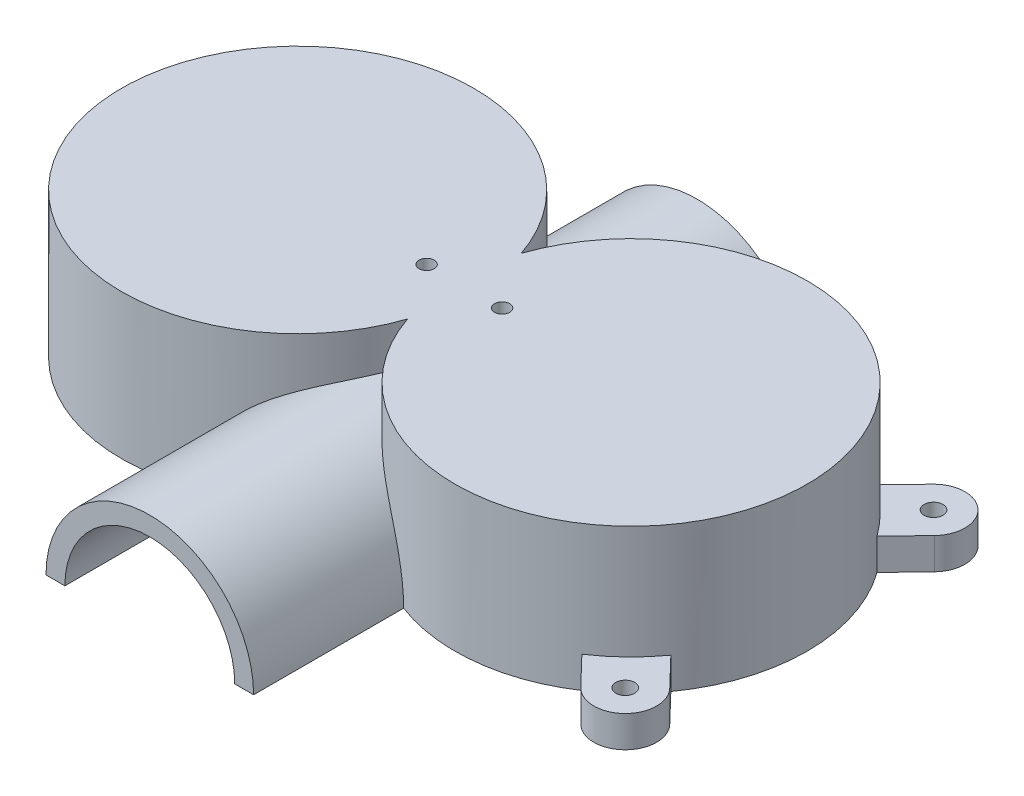
SolidWorks part; units mm, degrees
ref_plane "Front Plane" through (0, 0, 0) normal (0, 0, 1) x (1, 0, 0)
ref_plane "Top Plane" through (0, 0, 0) normal (0, 1, 0) x (1, 0, 0)
ref_plane "Right Plane" through (0, 0, 0) normal (1, 0, 0) x (0, 0, -1)
sketch "Sketch1" plane through (0, 0, 0) normal (0, 1, 0) x (1, 0, 0)
  line L0 (-26.5, 0) -> (26.5, 0) construction
  arc A0 (0, 9.0416) -> (0, -9.0416) centre (-26.5, 0) ccw
  arc A1 (0, -9.0416) -> (0, 9.0416) centre (26.5, 0) ccw
  dimension "D2" = 56
  dimension "D1" = 53
extrude "Boss-Extrude1" add sketch "Sketch1" along normal blind 23 contours A0 A1
shell "Shell1" [suppressed] thickness 3
sketch "Sketch2" plane through (0, 0, 0) normal (0, 1, 0) x (1, 0, 0)
  line L0 (-33.5, 33) -> (-33.5, 27.1109)
  line L1 (-23.5, 33) -> (-23.5, 27.8388)
  circle A0 centre (-28.5, 33) radius 1.5
  arc A1 (-23.5, 33) -> (-33.5, 33) centre (-28.5, 33) ccw
  arc A2 (-23.5, 27.8388) -> (-33.5, 27.1109) centre (-26.5, 0) ccw
  dimension "D3" = 3
  dimension "D4" = 10
  dimension "D5" = 56
  dimension "D1" = 33
  dimension "D2" = 28.5
  dimension "D6" = 26.5
extrude "Boss-Extrude2" add sketch "Sketch2" along normal blind 5
sketch "Sketch3" plane through (0, 0, 0) normal (0, 1, 0) x (1, 0, 0)
  line L0 (50.0744, 24.5) -> (50.0744, -24.5) construction
  line L1 (26.5, 0) -> (50.0744, -24.5) construction
  line L2 (0, 0) -> (50.0744, 0) construction
  line L3 (50.0744, 24.5) -> (26.5, 0) construction
  line L4 (46.4714, -27.9668) -> (41.9992, -23.319)
  line L5 (53.6773, -21.0332) -> (49.2051, -16.3854)
  line L6 (46.4714, 27.9668) -> (41.9992, 23.319)
  line L7 (53.6773, 21.0332) -> (49.2051, 16.3854)
  circle A0 centre (50.0744, 24.5) radius 1.5
  circle A1 centre (50.0744, -24.5) radius 1.5
  arc A2 (50.0744, 15.1079) -> (41.9992, 23.319) centre (26.5, 0) ccw
  arc A3 (53.6773, 21.0332) -> (46.4714, 27.9668) centre (50.0744, 24.5) ccw
  arc A4 (46.4714, -27.9668) -> (53.6773, -21.0332) centre (50.0744, -24.5) ccw
  arc A6 (41.9992, -23.319) -> (50.0744, -15.1079) centre (26.5, 0) ccw
  dimension "D3" = 56
  dimension "D5" = 3
  dimension "D6" = 10
  dimension "D1" = 49
  dimension "D2" = 26.5
  dimension "D4" = 34
extrude "Boss-Extrude3" add sketch "Sketch3" along normal blind 5 contours L7 A3 L6 A2 A0 | A6 L4 A4 L5 A1 region at (44.3687, 0, 25.5145) region at (53.4128, 0, -27.9695)
sketch "Sketch6" plane through (0, 0, 0) normal (0, 0, 1) x (1, 0, 0)
  line L0 (-16.5, 0) -> (16.5, 0)
  arc A0 (16.5, 0) -> (-16.5, 0) centre (0, 0) ccw
  dimension "D1" = 33
extrude "Boss-Extrude4" add sketch "Sketch6" against normal blind 37
extrude "Boss-Extrude5" add sketch "Sketch6<2>" along normal blind 50
sketch "Sketch6<2>" plane through (0, 0, 0) normal (0, 0, 1) x (1, 0, 0) same geometry as "Sketch6"
sketch "Sketch4" plane through (0, 0, 0) normal (0, 0, 1) x (1, 0, 0)
  line L0 (-13.5, 0) -> (13.5, 0)
  arc A0 (13.5, 0) -> (-13.5, 0) centre (0, 0) ccw
  dimension "D1" = 27
extrude "Cut-Extrude1" cut sketch "Sketch4" against normal through all both and the other way through all
sketch "Sketch5" plane through (0, 0, 0) normal (0, 1, 0) x (1, 0, 0)
  line L0 (26.5, 0) -> (-26.5, 0) construction
  circle A0 centre (-26.5, 0) radius 25
  circle A1 centre (26.5, 0) radius 25
  dimension "D2" = 50
  dimension "D1" = 53
extrude "Cut-Extrude4" cut sketch "Sketch5" along normal blind 20
sketch "Sketch7" plane through (0, 0, 0) normal (0, 1, 0) x (1, 0, 0)
  line L0 (-6, 0) -> (6, 0) construction
  circle A0 centre (-6, 0) radius 1.2
  circle A1 centre (6, 0) radius 1.2
  dimension "D1" = 2.4
  dimension "D2" = 12
extrude "Cut-Extrude6" cut sketch "Sketch7" along normal through all
